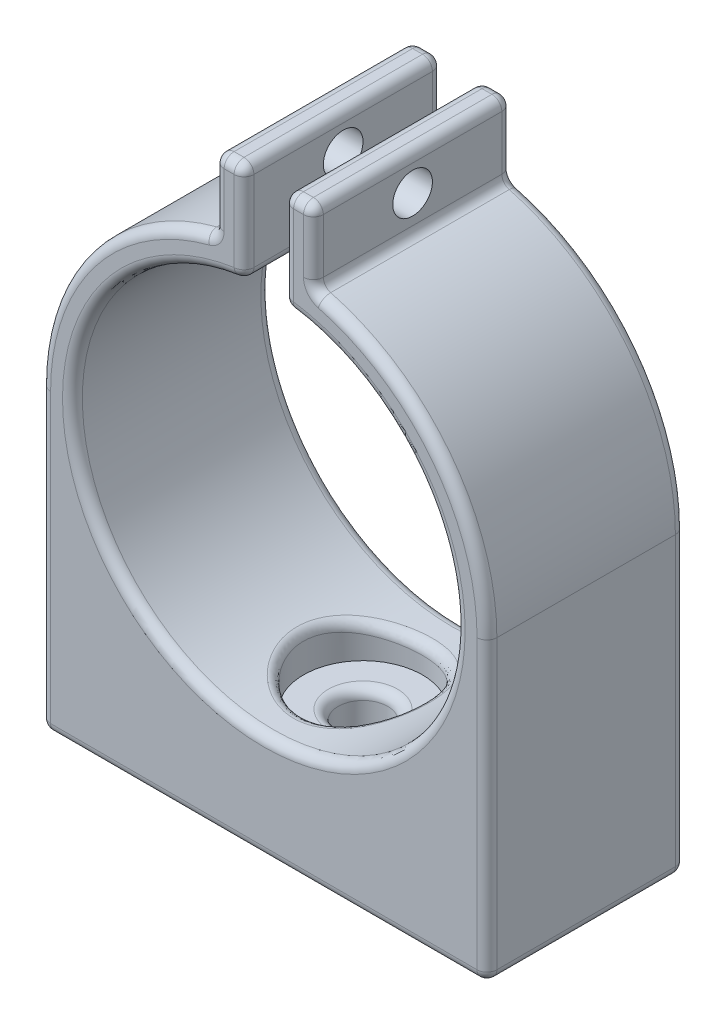
SolidWorks part; units mm, degrees
ref_plane "Front Plane" through (0, 0, 0) normal (0, 0, 1) x (1, 0, 0)
ref_plane "Top Plane" through (0, 0, 0) normal (0, 1, 0) x (1, 0, 0)
ref_plane "Right Plane" through (0, 0, 0) normal (1, 0, 0) x (0, 0, -1)
sketch "Sketch1" plane through (0, 0, 0) normal (0, 0, 1) x (1, 0, 0)
  line L2 (-2, 29.1961) -> (-5, 29.1961)
  line L4 (-5, 29.1961) -> (-5, 21.9374)
  line L5 (-2, 29.1961) -> (-2, 19.1961)
  line L6 (0, -19.3) -> (0, -30)
  line L7 (0, -30) -> (-22.5, -30)
  line L10 (-22.5, 0) -> (-22.5, -16.7471)
  line L12 (-22.5, -16.7471) -> (-22.5, -30)
  arc A0 (-2, 19.1961) -> (0, -19.3) centre (0, 0) ccw
  arc A1 (-5, 21.9374) -> (-22.5, 0) centre (0, 0) ccw
  point P3 (0, -24.65)
  dimension "D1" = 38.6
  dimension "D2" = 45
  dimension "D3" = 10
  dimension "D4" = 3
  dimension "D5" = 7.2587
  dimension "D6" = 5
  dimension "D11" = 30
extrude "Boss-Extrude1" add sketch "Sketch1" along normal blind 20
sketch "Sketch6" plane through (-5, 0, 0) normal (-1, 0, 0) x (0, 0, 1)
  circle A0 centre (10, 25.5668) radius 2
  dimension "D1" = 4
extrude "Cut-Extrude4" cut sketch "Sketch6" against normal blind 7
mirror "Mirror3" about plane through (0, -19.3, 20) normal (-1, 0, 0) of "Boss-Extrude1", "Cut-Extrude4"
sketch "Sketch7" plane through (0, -30, 0) normal (0, -1, 0) x (1, 0, 0)
  circle A0 centre (0, 10) radius 2.5
  dimension "D1" = 5
extrude "Cut-Extrude5" cut sketch "Sketch7" against normal blind 23 contours A0
sketch "Sketch8" plane through (0, -30, 0) normal (0, -1, 0) x (-1, 0, 0)
  circle A0 centre (0, -10) radius 6
  dimension "D1" = 12
extrude "Cut-Extrude6" cut sketch "Sketch8" along direction (0, 1, 0) on the side against the normal blind 5 from offset 8 contours A0 offset against normal yes
fillet "Fillet5" radius 1 37 edges at (-5.904, -18.3748, 8.9309) (2.5, -22, 10) (2.5, -30, 10) (17.5891, 14.0312, 0) (5, 25.5668, 0) (3.5, 29.1961, 0) (2, 24.1961, 0) (22.5, -15, 0) (17.5891, 14.0312, 20) (5, 25.5668, 20) (3.5, 29.1961, 20) (2, 24.1961, 20) (22.5, -15, 20) (22.5, -30, 10) (2, 19.1961, 10) (2, 29.1961, 10) (5, 29.1961, 10) (5, 21.9374, 10) (-17.5891, 14.0312, 0) (-22.5, -15, 0) (0, -30, 0) (0, -19.3, 0) (-2, 24.1961, 0) (-3.5, 29.1961, 0) (-5, 25.5668, 0) (-22.5, -15, 20) (0, -30, 20) (0, -19.3, 20) (-2, 24.1961, 20) (-3.5, 29.1961, 20) (-5, 25.5668, 20) (-5, 21.9374, 10) (-5, 29.1961, 10) (-2, 29.1961, 10) (-2, 19.1961, 10) (-22.5, -30, 10) (-17.5891, 14.0312, 20)
